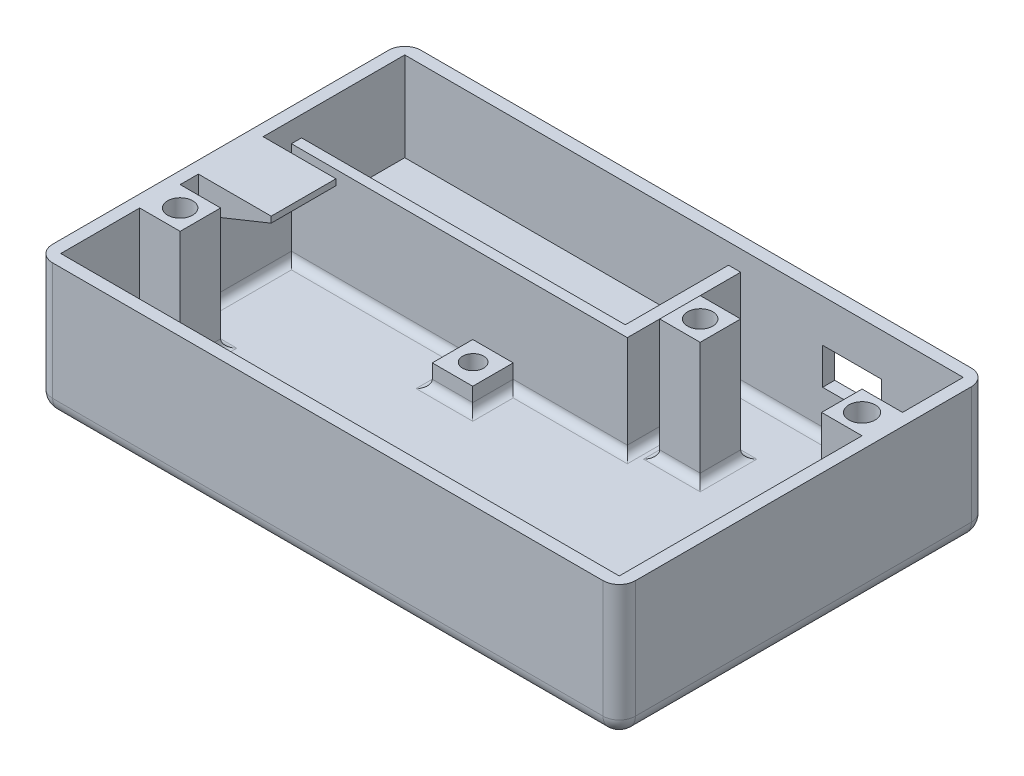
SolidWorks part; units mm, degrees
ref_plane "Alzado" through (0, 0, 0) normal (0, 0, 1) x (1, 0, 0)
ref_plane "Planta" through (0, 0, 0) normal (0, 1, 0) x (1, 0, 0)
ref_plane "Vista lateral" through (0, 0, 0) normal (1, 0, 0) x (0, 0, -1)
sketch "Croquis1" plane through (0, 0, 0) normal (0, 1, 0) x (1, 0, 0)
  line L1 (-69, -42.5) -> (69, -42.5)
  line L2 (-69, -42.5) -> (-69, 42.5)
  line L3 (-69, 42.5) -> (69, 42.5)
  line L4 (69, -42.5) -> (69, 42.5)
  line L5 (-69, -42.5) -> (69, 42.5) construction
  line L6 (-69, 42.5) -> (69, -42.5) construction
  point P0 (0, 0)
  dimension "D1" = 138
  dimension "D2" = 85
extrude "Saliente-Extruir1" add sketch "Croquis1" along normal blind 3
sketch "Croquis3" plane through (0, 3, 0) normal (0, 1, 0) x (1, 0, 0)
  line L4 (72, -45.5) -> (72, 45.5)
  line L5 (72, 45.5) -> (-72, 45.5)
  line L6 (-72, 45.5) -> (-72, -45.5)
  line L7 (-72, -45.5) -> (72, -45.5)
  line L24 (-69, 42.5) -> (69, 42.5)
  line L25 (69, 42.5) -> (69, -42.5)
  line L26 (69, -42.5) -> (-69, -42.5)
  line L27 (-69, -42.5) -> (-69, 42.5)
  dimension "D1" = 3
  dimension "D2" = 3
  dimension "D3" = 3
  dimension "D4" = 3
extrude "Saliente-Extruir3" add sketch "Croquis3" against normal up to surface (3 mm away) up to face at (0, 0, 0)
sketch "Croquis5" plane through (0, 3, 0) normal (0, 1, 0) x (1, 0, 0)
  line L4 (-72, -45.5) -> (72, -45.5)
  line L5 (72, -45.5) -> (72, 45.5)
  line L6 (72, 45.5) -> (-72, 45.5)
  line L7 (-72, 45.5) -> (-72, -45.5)
  line L8 (-72, -45.5) -> (72, -45.5)
  line L9 (72, -45.5) -> (72, 45.5)
  line L10 (72, 45.5) -> (-72, 45.5)
  line L11 (-72, 45.5) -> (-72, -45.5)
  dimension "D1" = 0
sketch "Croquis7" plane through (0, 3, 0) normal (0, 1, 0) x (1, 0, 0)
  line L0 (-69, -42.5) -> (69, -42.5)
  line L1 (69, -42.5) -> (69, 42.5)
  line L2 (69, 42.5) -> (-69, 42.5)
  line L3 (-69, 42.5) -> (-69, -42.5)
  line L4 (-72, -45.5) -> (72, -45.5)
  line L5 (72, -45.5) -> (72, 45.5)
  line L6 (72, 45.5) -> (-72, 45.5)
  line L7 (-72, 45.5) -> (-72, -45.5)
  line L8 (-72, -45.5) -> (72, -45.5)
  line L9 (72, -45.5) -> (72, 45.5)
  line L10 (72, 45.5) -> (-72, 45.5)
  line L11 (-72, 45.5) -> (-72, -45.5)
  dimension "D1" = 0
  dimension "D2" = 3
extrude "Saliente-Extruir4" add sketch "Croquis7" along normal blind 30
sketch "Croquis8" plane through (0, 3, 0) normal (0, 1, 0) x (1, 0, 0)
  line L0 (31.5, -33.5) -> (31.5, 9.5) construction
  line L1 (31.5, 9.5) -> (-19.2, 9.5) construction
  line L3 (-24.2, 4.5) -> (-14.2, 4.5)
  line L4 (-69, 42.5) -> (-69, -42.5) construction
  line L5 (26.5, -38.5) -> (36.5, -38.5)
  line L6 (26.5, -38.5) -> (26.5, -28.5)
  line L7 (26.5, -28.5) -> (36.5, -28.5)
  line L8 (36.5, -38.5) -> (36.5, -28.5)
  line L9 (26.5, -38.5) -> (36.5, -28.5) construction
  line L10 (26.5, -28.5) -> (36.5, -38.5) construction
  line L11 (-69, -42.5) -> (69, -42.5) construction
  line L12 (-24.2, 4.5) -> (-24.2, 14.5)
  line L17 (-24.2, 14.5) -> (-14.2, 14.5)
  line L18 (-14.2, 4.5) -> (-14.2, 14.5)
  line L19 (-24.2, 4.5) -> (-14.2, 14.5) construction
  line L20 (-24.2, 14.5) -> (-14.2, 4.5) construction
  point P0 (31.5, -33.5)
  dimension "D2" = 9
  dimension "D3" = 10
  dimension "D1" = 100.5
  dimension "D4" = 10
  dimension "D5" = 43
  dimension "D6" = 50.7
  dimension "D7" = 10
  dimension "D8" = 10
extrude "Saliente-Extruir5" add sketch "Croquis8" along normal blind 5.5
sketch "Croquis9" plane through (-69, 0, 0) normal (1, 0, 0) x (0, 0, -1)
  line L1 (-8.5, 33) -> (7.5, 33)
  line L2 (-8.5, 33) -> (-8.5, 31.5)
  line L3 (-8.5, 31.5) -> (7.5, 31.5)
  line L4 (7.5, 33) -> (7.5, 31.5)
  line L5 (-8.5, 33) -> (7.5, 31.5) construction
  line L6 (-8.5, 31.5) -> (7.5, 33) construction
  line L8 (-42.5, 33) -> (-42.5, 3) construction
  line L11 (11.0521, 8.5) -> (21.1388, 8.5) construction
  line L12 (45.5, 3) -> (-45.5, 3) construction
  point P0 (-0.5, 32.25)
  dimension "D1" = 5.5
  dimension "D2" = 16
  dimension "D3" = 34
  dimension "D4" = 1.5
  dimension "D5" = 24.5
extrude "Saliente-Extruir6" add sketch "Croquis9" along normal blind 18
sketch "Croquis10" plane through (0, 0, 8.5) normal (0, 0, 1) x (1, 0, 0)
  line L2 (-51, 31.5) -> (-69, 24.2275)
  line L5 (-51, 31.5) -> (-51, 33)
  line L8 (-69, 24.2275) -> (-69, 33)
  line L9 (-69, 33) -> (-51, 33)
  dimension "D1" = 68
extrude "Saliente-Extruir7" add sketch "Croquis10" against normal up to surface (16 mm away) up to face at (-60, 32.25, -7.5)
sketch "Croquis11" plane through (0, 3, 0) normal (0, 1, 0) x (1, 0, 0)
  line L1 (-69, 42.5) -> (14, 42.5)
  line L2 (-69, 42.5) -> (-69, 14.5)
  line L3 (-69, 14.5) -> (14, 14.5)
  line L4 (14, 42.5) -> (14, 14.5)
  line L6 (-14.2, 14.5) -> (-24.2, 14.5) construction
  dimension "D2" = 83
extrude "Saliente-Extruir8" add sketch "Croquis11" along normal blind 8
sketch "Croquis12" plane through (0, 11, 0) normal (0, 1, 0) x (1, 0, 0)
  line L0 (-69, 14.5) -> (14, 14.5) construction
  line L1 (-69, 42.5) -> (11, 42.5)
  line L2 (-69, 42.5) -> (-69, 17)
  line L3 (-69, 17) -> (11, 17)
  line L4 (11, 42.5) -> (11, 17)
  line L7 (-69, 14.5) -> (-69, 17)
  line L8 (11, 17) -> (11, 42.5)
  line L9 (14, 42.5) -> (14, 14.5)
  line L11 (-69, 42.5) -> (-69, 14.5)
  line L12 (-69, 14.5) -> (14, 14.5)
  line L13 (14, 14.5) -> (14, 42.5)
  line L14 (14, 42.5) -> (-69, 42.5)
  line L15 (-69, 42.5) -> (-69, 14.5)
  line L16 (-69, 14.5) -> (14, 14.5)
  line L17 (14, 14.5) -> (14, 42.5)
  line L18 (14, 42.5) -> (-69, 42.5)
  line M5 (-69, 42.5) -> (-69, 14.5)
  line M6 (-69, 14.5) -> (14, 14.5)
  line M7 (14, 14.5) -> (14, 42.5)
  line M8 (14, 42.5) -> (-69, 42.5)
  dimension "D1" = 2.5
  dimension "D2" = 80
  dimension "D3" = 0
extrude "Saliente-Extruir9" add sketch "Croquis12" along normal blind 17 contours L4 L3 M8 M5 M6 M7 region at (12.5, 11, -41.624)
sketch "Croquis14" plane through (11, 0, 0) normal (-1, 0, 0) x (0, 0, 1)
  line L0 (-40, 15.5) -> (-42.5, 15.5) construction
  line L1 (-42.5, 28) -> (-42.5, 11) construction
  line L2 (-42.5, 11) -> (-17, 11) construction
  circle A0 centre (-40, 15.5) radius 2.5
  dimension "D1" = 5
  dimension "D2" = 4.5
extrude "Cortar-Extruir1" cut sketch "Croquis14" against normal up to next
sketch "Croquis15" plane through (0, 8.5, 0) normal (0, 1, 0) x (1, 0, 0)
  line L0 (-24.2, 4.5) -> (-14.2, 4.5) construction
  line L1 (-14.2, 4.5) -> (-14.2, 14.5) construction
  line L2 (26.5, -38.5) -> (36.5, -38.5) construction
  line L3 (36.5, -38.5) -> (36.5, -28.5) construction
  circle A1 centre (31.5, -33.5) radius 2.6
  point P16 (0, 0)
  point P18 (0, 0)
  point P20 (31.5, -38.5)
  point P21 (36.5, -33.5)
  dimension "D2" = 5.2
extrude "Cortar-Extruir2" cut sketch "Croquis15" against normal up to next
sketch "Croquis16" plane through (0, 0, -42.5) normal (0, 0, 1) x (1, 0, 0)
  line L0 (69, 33) -> (14, 33) construction
  line L1 (69, 33) -> (-69, 33) construction
  line L2 (69, 33) -> (69, 3) construction
  line L3 (34.25, 13.5) -> (48.75, 13.5)
  line L4 (34.25, 13.5) -> (34.25, 22.5)
  line L5 (34.25, 22.5) -> (48.75, 22.5)
  line L6 (48.75, 13.5) -> (48.75, 22.5)
  line L7 (34.25, 13.5) -> (48.75, 22.5) construction
  line L8 (34.25, 22.5) -> (48.75, 13.5) construction
  point P5 (41.5, 18)
  point P10 (41.5, 33)
  point P13 (69, 18)
  dimension "D1" = 55
  dimension "D2" = 14.5
  dimension "D3" = 9
extrude "Cortar-Extruir3" cut sketch "Croquis16" against normal up to next
sketch "Croquis17" plane through (0, 3, 0) normal (0, 1, 0) x (1, 0, 0)
  line L1 (-69, -23) -> (-59, -23)
  line L2 (-69, -23) -> (-69, -13)
  line L3 (-69, -13) -> (-59, -13)
  line L4 (-59, -23) -> (-59, -13)
  line L5 (69, -42.5) -> (69, 42.5) construction
  line L6 (69, 17.5) -> (59, 17.5)
  line L7 (69, 17.5) -> (69, 27.5)
  line L8 (69, 27.5) -> (59, 27.5)
  line L9 (59, 17.5) -> (59, 27.5)
  line L10 (-69, 14.5) -> (-69, -42.5) construction
  line L11 (19, 17.5) -> (29, 17.5)
  line L12 (19, 17.5) -> (19, 27.5)
  line L13 (19, 27.5) -> (29, 27.5)
  line L14 (29, 17.5) -> (29, 27.5)
  line L15 (-69, -8.5) -> (-69, -27.5) construction
  line L16 (14, 42.5) -> (14, 14.5) construction
  line L17 (69, 42.5) -> (-69, 42.5) construction
  line L18 (-72, -45.5) -> (72, -45.5) construction
  point P4 (-69, -18)
  point P5 (-69, -18)
  point P21 (0, 0)
  point P26 (29, 22.5)
  point P27 (-59, -18)
  point P28 (59, 22.5)
  dimension "D1" = 10
  dimension "D2" = 10
  dimension "D3" = 19
  dimension "D4" = 10
  dimension "D5" = 10
  dimension "D6" = 10
  dimension "D7" = 10
  dimension "D8" = 15
  dimension "D9" = 5
  dimension "D10" = 27.5
extrude "Saliente-Extruir10" add sketch "Croquis17" along normal up to surface (30 mm away) up to face at (-30, 33, 0.25)
sketch "Croquis18" plane through (0, 33, 0) normal (0, 1, 0) x (1, 0, 0)
  line L0 (-69, -23) -> (-59, -13) construction
  line L1 (19, 17.5) -> (29, 27.5) construction
  line L2 (59, 17.5) -> (69, 27.5) construction
  circle A0 centre (-64, -18) radius 3.1
  circle A1 centre (24, 22.5) radius 3.1
  circle A2 centre (64, 22.5) radius 3.25
  dimension "D1" = 6.2
  dimension "D2" = 6.2
  dimension "D3" = 6.5
extrude "Cortar-Extruir4" cut sketch "Croquis18" against normal up to next
fillet "Redondeo1" radius 2 26 edges at (24, 3, -17.5) (29, 3, -22.5) (24, 3, -27.5) (19, 3, -22.5) (31.5, 3, 28.5) (26.5, 3, 33.5) (31.5, 3, 38.5) (36.5, 3, 33.5) (59, 3, -22.5) (64, 3, -17.5) (69, 3, 12.5) (0, 3, 42.5) (-69, 3, 32.75) (-64, 3, 23) (-59, 3, 18) (-64, 3, 13) (-69, 3, -0.75) (-46.6, 3, -14.5) (-24.2, 3, -9.5) (-19.2, 3, -4.5) (-14.2, 3, -9.5) (-0.1, 3, -14.5) (14, 3, -28.5) (41.5, 3, -42.5) (69, 3, -35) (64, 3, -27.5)
fillet "Redondeo2" radius 4 8 edges at (72, 0, 0) (0, 0, -45.5) (0, 0, 45.5) (-72, 0, 0) (-72, 16.5, 45.5) (-72, 16.5, -45.5) (72, 16.5, -45.5) (72, 16.5, 45.5)
sketch "Croquis21" plane through (0, 8.5, 0) normal (0, 1, 0) x (1, 0, 0)
  line L1 (-69, 42.5) -> (-69, 7.5) construction
  line L3 (-69, 14.5) -> (14, 14.5) construction
  circle A0 centre (-19.3, 9.7) radius 2.6
  dimension "D3" = 5.2
  dimension "D1" = 49.7
  dimension "D2" = 4.8
extrude "Cortar-Extruir5" cut sketch "Croquis21" against normal up to next
